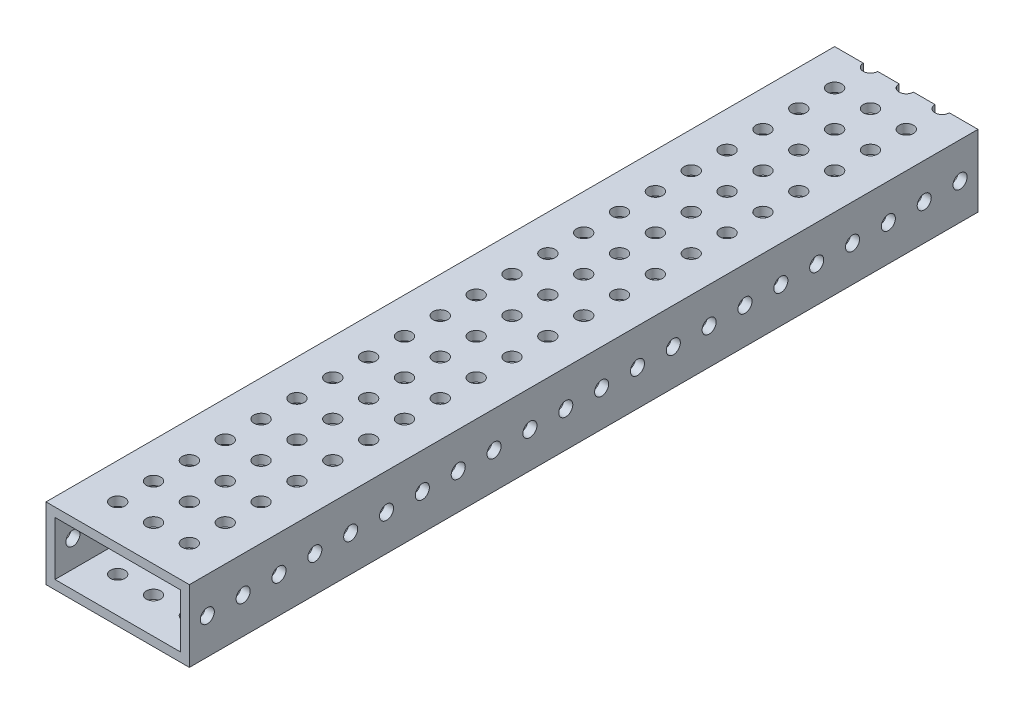
SolidWorks part; units mm, degrees
material "6061-T6 (SS)"
ref_plane "Front Plane" through (0, 0, 0) normal (0, 0, 1) x (1, 0, 0)
ref_plane "Top Plane" through (0, 0, 0) normal (0, 1, 0) x (1, 0, 0)
ref_plane "Right Plane" through (0, 0, 0) normal (1, 0, 0) x (0, 0, -1)
sketch "Sketch1" plane through (0, 0, 0) normal (0, 0, 1) x (1, 0, 0)
  line L0 (-22.225, 9.525) -> (22.225, 9.525)
  line L1 (-25.4, 12.7) -> (25.4, 12.7)
  line L2 (-25.4, 12.7) -> (-25.4, -12.7)
  line L3 (-25.4, -12.7) -> (25.4, -12.7)
  line L4 (25.4, 12.7) -> (25.4, -12.7)
  line L5 (22.225, 9.525) -> (22.225, -9.525)
  line L6 (-22.225, -9.525) -> (22.225, -9.525)
  line L7 (-22.225, 9.525) -> (-22.225, -9.525)
  line L8 (-25.4, 12.7) -> (25.4, -12.7) construction
  line L9 (25.4, 12.7) -> (-25.4, -12.7) construction
  point P5 (0, 0)
  dimension "D1" = 50.8
  dimension "D2" = 25.4
  dimension "D3" = 3.175
extrude "Boss-Extrude1" add sketch "Sketch1" along normal mid plane 279.4
sketch "Sketch2" plane through (0, 12.7, 0) normal (0, 1, 0) x (1, 0, 0)
  line L0 (25.4, -139.7) -> (-25.4, -139.7) construction
  line L1 (-25.4, -139.7) -> (-25.4, 139.7) construction
  line L2 (-12.7, -127) -> (0, -127) construction
  line L3 (0, -127) -> (12.7, -127) construction
  line L4 (25.4, 139.7) -> (-25.4, 139.7) construction
  circle A0 centre (0, -127) radius 2.5527
  circle A1 centre (12.7, -127) radius 2.5527
  circle A2 centre (-12.7, -127) radius 2.5527
  circle A3 centre (-12.7, -114.3) radius 2.5527
  circle A4 centre (0, -114.3) radius 2.5527
  circle A5 centre (12.7, -114.3) radius 2.5527
  circle A6 centre (-12.7, -101.6) radius 2.5527
  circle A7 centre (0, -101.6) radius 2.5527
  circle A8 centre (12.7, -101.6) radius 2.5527
  circle A9 centre (-12.7, -88.9) radius 2.5527
  circle A10 centre (0, -88.9) radius 2.5527
  circle A11 centre (12.7, -88.9) radius 2.5527
  circle A12 centre (-12.7, -76.2) radius 2.5527
  circle A13 centre (0, -76.2) radius 2.5527
  circle A14 centre (12.7, -76.2) radius 2.5527
  circle A15 centre (-12.7, -63.5) radius 2.5527
  circle A16 centre (0, -63.5) radius 2.5527
  circle A17 centre (12.7, -63.5) radius 2.5527
  circle A18 centre (-12.7, -50.8) radius 2.5527
  circle A19 centre (0, -50.8) radius 2.5527
  circle A20 centre (12.7, -50.8) radius 2.5527
  circle A21 centre (-12.7, -38.1) radius 2.5527
  circle A22 centre (0, -38.1) radius 2.5527
  circle A23 centre (12.7, -38.1) radius 2.5527
  circle A24 centre (-12.7, -25.4) radius 2.5527
  circle A25 centre (0, -25.4) radius 2.5527
  circle A26 centre (12.7, -25.4) radius 2.5527
  circle A27 centre (-12.7, -12.7) radius 2.5527
  circle A28 centre (0, -12.7) radius 2.5527
  circle A29 centre (12.7, -12.7) radius 2.5527
  circle A30 centre (-12.7, 0) radius 2.5527
  circle A31 centre (0, 0) radius 2.5527
  circle A32 centre (12.7, 0) radius 2.5527
  circle A33 centre (-12.7, 12.7) radius 2.5527
  circle A34 centre (0, 12.7) radius 2.5527
  circle A35 centre (12.7, 12.7) radius 2.5527
  circle A36 centre (-12.7, 25.4) radius 2.5527
  circle A37 centre (0, 25.4) radius 2.5527
  circle A38 centre (12.7, 25.4) radius 2.5527
  circle A39 centre (-12.7, 38.1) radius 2.5527
  circle A40 centre (0, 38.1) radius 2.5527
  circle A41 centre (12.7, 38.1) radius 2.5527
  circle A42 centre (-12.7, 50.8) radius 2.5527
  circle A43 centre (0, 50.8) radius 2.5527
  circle A44 centre (12.7, 50.8) radius 2.5527
  circle A45 centre (-12.7, 63.5) radius 2.5527
  circle A46 centre (0, 63.5) radius 2.5527
  circle A47 centre (12.7, 63.5) radius 2.5527
  circle A48 centre (-12.7, 76.2) radius 2.5527
  circle A49 centre (0, 76.2) radius 2.5527
  circle A50 centre (12.7, 76.2) radius 2.5527
  circle A51 centre (-12.7, 88.9) radius 2.5527
  circle A52 centre (0, 88.9) radius 2.5527
  circle A53 centre (12.7, 88.9) radius 2.5527
  circle A54 centre (-12.7, 101.6) radius 2.5527
  circle A55 centre (0, 101.6) radius 2.5527
  circle A56 centre (12.7, 101.6) radius 2.5527
  circle A57 centre (-12.7, 114.3) radius 2.5527
  circle A58 centre (0, 114.3) radius 2.5527
  circle A59 centre (12.7, 114.3) radius 2.5527
  circle A60 centre (-12.7, 127) radius 2.5527
  circle A61 centre (0, 127) radius 2.5527
  circle A62 centre (12.7, 127) radius 2.5527
  circle A63 centre (-12.7, 139.7) radius 2.5527
  circle A64 centre (0, 139.7) radius 2.5527
  circle A65 centre (12.7, 139.7) radius 2.5527
  circle A66 centre (-12.7, 152.4) radius 2.5527
  circle A67 centre (0, 152.4) radius 2.5527
  circle A68 centre (12.7, 152.4) radius 2.5527
  circle A69 centre (-12.7, 165.1) radius 2.5527
  circle A70 centre (0, 165.1) radius 2.5527
  circle A71 centre (12.7, 165.1) radius 2.5527
  circle A72 centre (-12.7, 177.8) radius 2.5527
  circle A73 centre (0, 177.8) radius 2.5527
  circle A74 centre (12.7, 177.8) radius 2.5527
  circle A75 centre (-12.7, 190.5) radius 2.5527 construction
  circle A76 centre (0, 190.5) radius 2.5527 construction
  circle A77 centre (12.7, 190.5) radius 2.5527 construction
  circle A78 centre (-12.7, 203.2) radius 2.5527
  circle A79 centre (0, 203.2) radius 2.5527
  circle A80 centre (12.7, 203.2) radius 2.5527
  circle A81 centre (-12.7, 215.9) radius 2.5527
  circle A82 centre (0, 215.9) radius 2.5527
  circle A83 centre (12.7, 215.9) radius 2.5527
  circle A84 centre (-12.7, 228.6) radius 2.5527
  circle A85 centre (0, 228.6) radius 2.5527
  circle A86 centre (12.7, 228.6) radius 2.5527
  circle A87 centre (-12.7, 241.3) radius 2.5527
  circle A88 centre (0, 241.3) radius 2.5527
  circle A89 centre (12.7, 241.3) radius 2.5527
  circle A90 centre (-12.7, 254) radius 2.5527
  circle A91 centre (0, 254) radius 2.5527
  circle A92 centre (12.7, 254) radius 2.5527
  circle A93 centre (-12.7, 266.7) radius 2.5527
  circle A94 centre (0, 266.7) radius 2.5527
  circle A95 centre (12.7, 266.7) radius 2.5527
  circle A96 centre (-12.7, 279.4) radius 2.5527
  circle A97 centre (0, 279.4) radius 2.5527
  circle A98 centre (12.7, 279.4) radius 2.5527
  circle A99 centre (-12.7, 292.1) radius 2.5527
  circle A100 centre (0, 292.1) radius 2.5527
  circle A101 centre (12.7, 292.1) radius 2.5527
  circle A108 centre (-12.7, 317.5) radius 2.5527 [skipped]
  circle A109 centre (0, 317.5) radius 2.5527 [skipped]
  circle A110 centre (12.7, 317.5) radius 2.5527 [skipped]
  circle A111 centre (-12.7, 304.8) radius 2.5527 [skipped]
  circle A112 centre (0, 304.8) radius 2.5527 [skipped]
  circle A113 centre (12.7, 304.8) radius 2.5527 [skipped]
  circle A114 centre (12.7, 304.8) radius 2.5527
  circle A115 centre (0, 304.8) radius 2.5527
  circle A116 centre (-12.7, 304.8) radius 2.5527
  circle A117 centre (12.7, 317.5) radius 2.5527
  circle A118 centre (0, 317.5) radius 2.5527
  circle A119 centre (-12.7, 317.5) radius 2.5527
  circle A120 centre (12.7, 330.2) radius 2.5527
  circle A121 centre (0, 330.2) radius 2.5527
  circle A122 centre (-12.7, 330.2) radius 2.5527
  circle A123 centre (12.7, 342.9) radius 2.5527
  circle A124 centre (0, 342.9) radius 2.5527
  circle A125 centre (-12.7, 342.9) radius 2.5527
  circle A126 centre (12.7, 355.6) radius 2.5527
  circle A127 centre (0, 355.6) radius 2.5527
  circle A128 centre (-12.7, 355.6) radius 2.5527
  circle A129 centre (12.7, 368.3) radius 2.5527
  circle A130 centre (0, 368.3) radius 2.5527
  circle A131 centre (-12.7, 368.3) radius 2.5527
  circle A132 centre (12.7, 381) radius 2.5527
  circle A133 centre (0, 381) radius 2.5527
  circle A134 centre (-12.7, 381) radius 2.5527
  circle A135 centre (12.7, 393.7) radius 2.5527
  circle A136 centre (0, 393.7) radius 2.5527
  circle A137 centre (-12.7, 393.7) radius 2.5527
  circle A138 centre (12.7, 406.4) radius 2.5527
  circle A139 centre (0, 406.4) radius 2.5527
  circle A140 centre (-12.7, 406.4) radius 2.5527
  circle A141 centre (12.7, 419.1) radius 2.5527
  circle A142 centre (0, 419.1) radius 2.5527
  circle A143 centre (-12.7, 419.1) radius 2.5527
  circle A144 centre (12.7, 431.8) radius 2.5527
  circle A145 centre (0, 431.8) radius 2.5527
  circle A146 centre (-12.7, 431.8) radius 2.5527
  circle A147 centre (12.7, 444.5) radius 2.5527
  circle A148 centre (0, 444.5) radius 2.5527
  circle A149 centre (-12.7, 444.5) radius 2.5527
  circle A150 centre (12.7, 457.2) radius 2.5527
  circle A151 centre (0, 457.2) radius 2.5527
  circle A152 centre (-12.7, 457.2) radius 2.5527
  dimension "D2" = 5.1054
  dimension "D4" = 12.7
  dimension "D1" = 12.7
  dimension "D3" = 25.4
  dimension "D6" = 12.7
  dimension "D7" = 152.4
  dimension "D5" = 36
  dimension "D8" = 14
extrude "Cut-Extrude1" cut sketch "Sketch2" against normal through all
sketch "Sketch4" plane through (25.4, 0, 0) normal (1, 0, 0) x (0, 0, -1)
  line L1 (-139.7, -12.7) -> (-139.7, 12.7) construction
  line L2 (-139.7, -12.7) -> (139.7, -12.7) construction
  circle A2 centre (-133.35, 0) radius 2.4892
  circle A3 centre (-120.65, 0) radius 2.4892
  circle A16 centre (-107.95, 0) radius 2.4892
  circle A17 centre (-95.25, 0) radius 2.4892
  circle A18 centre (-82.55, 0) radius 2.4892
  circle A19 centre (298.45, 0) radius 2.4892
  circle A20 centre (311.15, 0) radius 2.4892
  circle A21 centre (323.85, 0) radius 2.4892
  circle A22 centre (336.55, 0) radius 2.4892
  circle A23 centre (349.25, 0) radius 2.4892
  circle A24 centre (361.95, 0) radius 2.4892
  circle A25 centre (374.65, 0) radius 2.4892
  circle A26 centre (387.35, 0) radius 2.4892
  circle A27 centre (400.05, 0) radius 2.4892
  circle A28 centre (412.75, 0) radius 2.4892
  circle A29 centre (425.45, 0) radius 2.4892
  circle A30 centre (438.15, 0) radius 2.4892
  circle A31 centre (450.85, 0) radius 2.4892
  circle A32 centre (463.55, 0) radius 2.4892
  circle A35 centre (-69.85, 0) radius 2.4892
  circle A36 centre (-57.15, 0) radius 2.4892
  circle A37 centre (-44.45, 0) radius 2.4892
  circle A38 centre (-31.75, 0) radius 2.4892
  circle A39 centre (-19.05, 0) radius 2.4892
  circle A40 centre (-6.35, 0) radius 2.4892
  circle A41 centre (6.35, 0) radius 2.4892
  circle A42 centre (19.05, 0) radius 2.4892
  circle A43 centre (31.75, 0) radius 2.4892
  circle A44 centre (44.45, 0) radius 2.4892
  circle A45 centre (57.15, 0) radius 2.4892
  circle A46 centre (69.85, 0) radius 2.4892
  circle A47 centre (82.55, 0) radius 2.4892
  circle A48 centre (95.25, 0) radius 2.4892
  circle A49 centre (107.95, 0) radius 2.4892
  circle A50 centre (120.65, 0) radius 2.4892
  circle A51 centre (133.35, 0) radius 2.4892
  circle A52 centre (146.05, 0) radius 2.4892
  circle A53 centre (158.75, 0) radius 2.4892
  circle A54 centre (171.45, 0) radius 2.4892
  circle A55 centre (184.15, 0) radius 2.4892
  circle A56 centre (196.85, 0) radius 2.4892
  circle A57 centre (209.55, 0) radius 2.4892
  circle A58 centre (222.25, 0) radius 2.4892
  circle A59 centre (234.95, 0) radius 2.4892
  circle A60 centre (247.65, 0) radius 2.4892
  circle A61 centre (260.35, 0) radius 2.4892
  circle A62 centre (273.05, 0) radius 2.4892
  circle A63 centre (285.75, 0) radius 2.4892
  dimension "D2" = 4.9784
  dimension "D1" = 6.35
  dimension "D3" = 12.7
  dimension "D4" = 12.7
  dimension "D5" = 34
  dimension "D6" = 10
  dimension "D7" = 6
extrude "Cut-Extrude3" cut sketch "Sketch4" against normal through all
